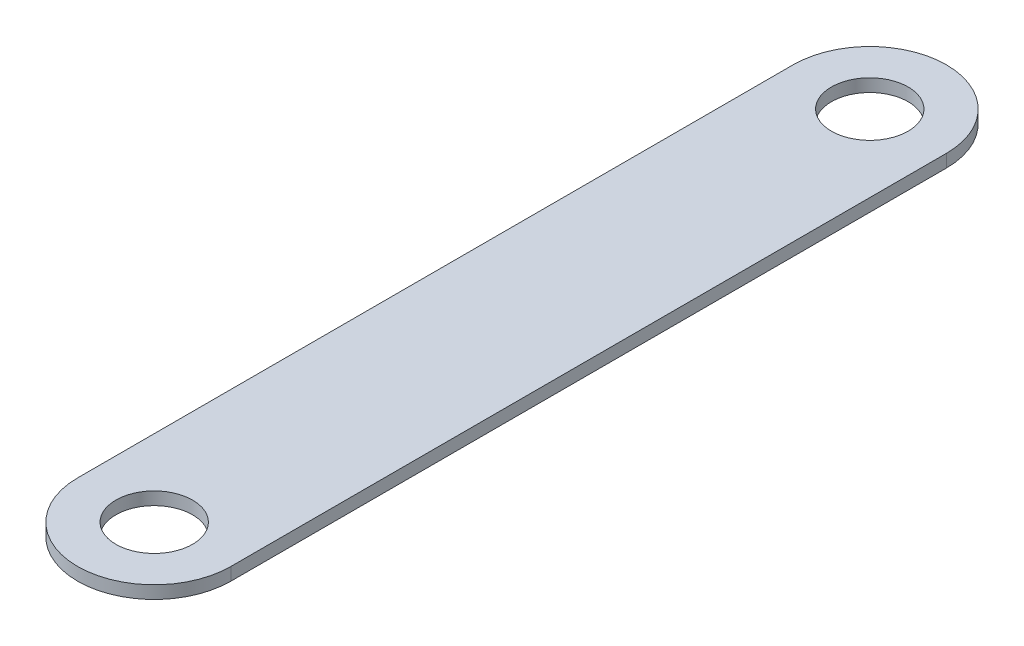
SolidWorks part; units mm, degrees
ref_plane "Front Plane" through (0, 0, 0) normal (0, 0, 1) x (1, 0, 0)
ref_plane "Top Plane" through (0, 0, 0) normal (0, 1, 0) x (1, 0, 0)
ref_plane "Right Plane" through (0, 0, 0) normal (1, 0, 0) x (0, 0, -1)
sketch "Sketch1" plane through (0, 0, 0) normal (0, 1, 0) x (1, 0, 0)
  line L0 (-38.1, 0) -> (-38.1, -355.6)
  line L1 (38.1, 0) -> (38.1, -355.6)
  arc A0 (38.1, 0) -> (-38.1, 0) centre (0, 0) ccw
  arc A1 (-38.1, -355.6) -> (38.1, -355.6) centre (0, -355.6) ccw
  circle A2 centre (0, 0) radius 19.05
  circle A3 centre (0, -355.6) radius 19.05
  dimension "D1" = 76.2
  dimension "D2" = 76.2
  dimension "D4" = 38.1
  dimension "D5" = 38.1
  dimension "D3" = 355.6
extrude "Boss-Extrude1" add sketch "Sketch1" along normal blind 6.35
